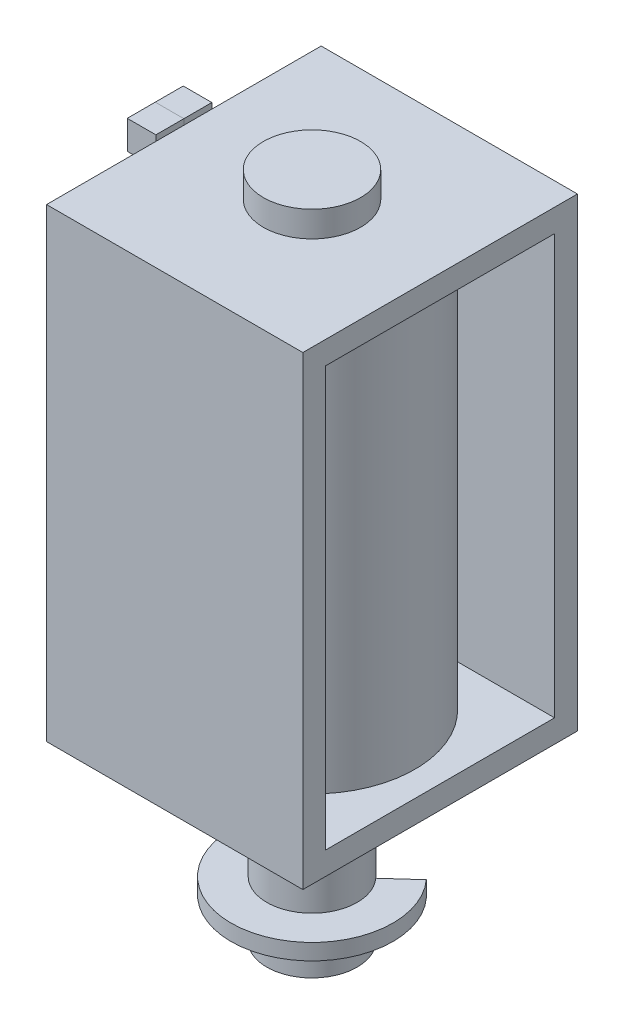
SolidWorks part; units mm, degrees
ref_plane "Front Plane" through (0, 0, 0) normal (0, 0, 1) x (1, 0, 0)
ref_plane "Top Plane" through (0, 0, 0) normal (0, 1, 0) x (1, 0, 0)
ref_plane "Right Plane" through (0, 0, 0) normal (1, 0, 0) x (0, 0, -1)
sketch "Sketch3" plane through (0, 0, 0) normal (1, 0, 0) x (0, 0, -1)
  line L1 (6.096, -10.3251) -> (-6.096, -10.3251)
  line L2 (6.096, -10.3251) -> (6.096, 10.3251)
  line L3 (6.096, 10.3251) -> (-6.096, 10.3251)
  line L4 (-6.096, -10.3251) -> (-6.096, 10.3251)
  line L5 (6.096, -10.3251) -> (-6.096, 10.3251) construction
  line L6 (6.096, 10.3251) -> (-6.096, -10.3251) construction
  line L7 (5.08, -9.3091) -> (-5.08, -9.3091)
  line L8 (5.08, -9.3091) -> (5.08, 9.3091)
  line L9 (5.08, 9.3091) -> (-5.08, 9.3091)
  line L10 (-5.08, -9.3091) -> (-5.08, 9.3091)
  line L11 (5.08, -9.3091) -> (-5.08, 9.3091) construction
  line L12 (5.08, 9.3091) -> (-5.08, -9.3091) construction
  point P0 (0, 0)
  point P6 (0, 0)
  dimension "D1" = 20.6502
  dimension "D2" = 12.192
  dimension "D3" = 1.016
  dimension "D4" = 1.016
extrude "Boss-Extrude3" add sketch "Sketch3" along normal mid plane 11.3792 separate body
sketch "Sketch2" plane through (0, 0, 0) normal (0, 1, 0) x (1, 0, 0)
  circle A0 centre (0, 0) radius 4.572
  dimension "D1" = 9.144
extrude "Boss-Extrude2" add sketch "Sketch2" along normal mid plane 18.796
sketch "Sketch4" plane through (0, 10.3251, 0) normal (0, 1, 0) x (1, 0, 0)
  circle A0 centre (0, 0) radius 0.7747
  circle A1 centre (0, 0) radius 2.159
  dimension "D1" = 4.318
  dimension "D2" = 1.5494
extrude "Boss-Extrude4" add sketch "Sketch4" along normal blind 1.143 separate body contours A0 | A1 A0 region at (0, 10.3251, 0) region at (-2.0979, 10.3251, 0)
sketch "Sketch5" plane through (0, -10.3251, 0) normal (0, -1, 0) x (1, 0, 0)
  circle A0 centre (0, 0) radius 2.0066
  dimension "D1" = 4.0132
extrude "Boss-Extrude5" add sketch "Sketch5" along normal blind 7.874
ref_plane "Plane1" through (0, -15.7099, 0) normal (0, -1, 0) x (-1, 0, 0)
sketch "Sketch6" plane through (0, -15.7099, 0) normal (0, -1, 0) x (1, 0, 0)
  line L0 (-2.667, -2.4093) -> (-1.489, -1.3451)
  line L1 (1.489, -1.3451) -> (2.667, -2.4093)
  line L2 (-3.5689, -1.3451) -> (3.5689, -1.3451) construction
  line L3 (-5.0182, -2.4093) -> (5.0182, -2.4093) construction
  arc A0 (2.667, -2.4093) -> (-2.667, -2.4093) centre (0, 0) ccw
  circle A1 centre (0, 0) radius 2.0066 construction
  circle A2 centre (0, 0) radius 2.0066 construction
  arc A3 (1.489, -1.3451) -> (-1.489, -1.3451) centre (0, 0) ccw
  point P13 (0, -1.3451)
  point P17 (0, -2.4093)
  dimension "D1" = 7.1882
  dimension "D3" = 5.334
extrude "Boss-Extrude11" add sketch "Sketch6" along normal blind 0.7112
sketch "Sketch7" plane through (-5.6896, 0, 0) normal (-1, 0, 0) x (0, 0, 1)
  line L0 (-1.2429, 10.5791) -> (-1.2429, 9.3091)
  line L1 (-5.08, 9.3091) -> (5.08, 9.3091) construction
  line L2 (-1.2429, 9.3091) -> (0, 9.3091)
  line L3 (0, 9.3091) -> (0, 10.5791)
  line L4 (0, 10.5791) -> (-1.2429, 10.5791)
  line L5 (0, 10.5791) -> (1.2429, 10.5791)
  line L6 (1.2429, 10.5791) -> (1.2429, 9.3091)
  line L7 (1.2429, 9.3091) -> (0, 9.3091)
  line L8 (-5.08, 9.3091) -> (5.08, 9.3091) construction
  point P8 (0, 9.3091)
  line M10 (6.096, 10.3251) -> (-6.096, 10.3251)
  line M16 (-5.08, 9.3091) -> (5.08, 9.3091)
  dimension "D1" = 2.4857
  dimension "D2" = 1.27
extrude "Boss-Extrude12" add sketch "Sketch7" along normal blind 1.27 separate body contours L3 L4 L0 M10 | L3 L0 M16 M10 region at (-5.6896, 10.4521, -0.6214) region at (-5.6896, 9.8171, -0.6214)
extrude "Boss-Extrude13" add sketch "Sketch7<3>" along normal blind 1.27 separate body contours L6 L5 L3 M10 | L6 L3 M10 M16 region at (-5.6896, 10.4521, 0.6214) region at (-5.6896, 9.8171, 0.6214)
sketch "Sketch7<3>" plane through (-5.6896, 0, 0) normal (-1, 0, 0) x (0, 0, 1) same geometry as "Sketch7"
